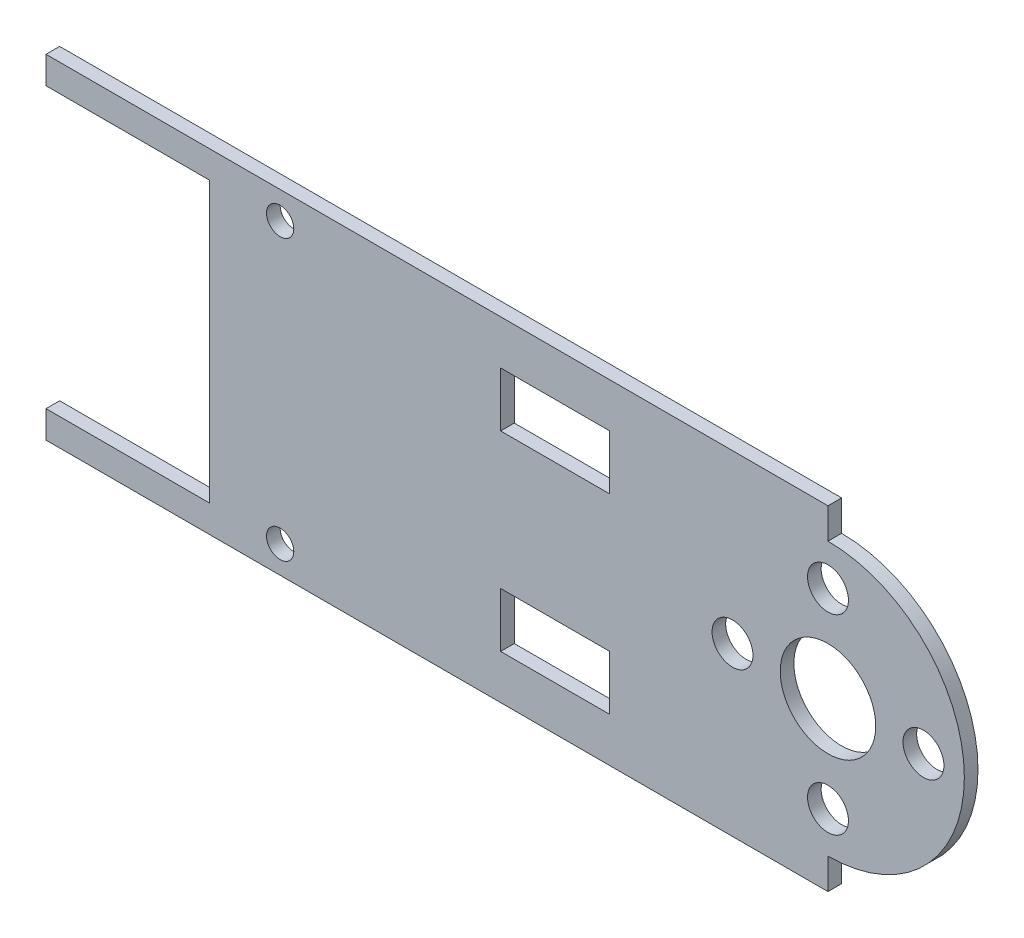
SolidWorks part; units mm, degrees
ref_plane "Front Plane" through (0, 0, 0) normal (0, 0, 1) x (1, 0, 0)
ref_plane "Top Plane" through (0, 0, 0) normal (0, 1, 0) x (1, 0, 0)
ref_plane "Right Plane" through (0, 0, 0) normal (1, 0, 0) x (0, 0, -1)
sketch "Sketch1" plane through (0, 0, 0) normal (0, 0, 1) x (1, 0, 0)
  line L0 (-5.1665, 12.25) -> (-17.1665, 12.25)
  line L1 (-5.1665, 12.25) -> (5.1665, 12.25)
  line L2 (-5.1665, 10.25) -> (-5.1665, -10.25)
  line L3 (-5.1665, -12.25) -> (5.1665, -12.25)
  line L5 (-5.1665, 12.25) -> (5.1665, -12.25) construction
  line L6 (-5.1665, -12.25) -> (5.1665, 12.25) construction
  line L7 (-17.1665, 12.25) -> (-17.1665, 10.25)
  line L8 (-17.1665, 10.25) -> (-5.1665, 10.25)
  line L9 (-5.1665, -12.25) -> (-17.1665, -12.25)
  line L10 (-17.1665, -12.25) -> (-17.1665, -10.25)
  line L11 (-17.1665, -10.25) -> (-5.1665, -10.25)
  line L12 (5.1665, 12.25) -> (40.1665, 12.25)
  line L13 (40.1665, 12.25) -> (40.1665, 10)
  line L14 (40.1665, -12.25) -> (5.1665, -12.25)
  line L16 (40.1665, -10) -> (40.1665, -12.25)
  line L17 (16.1665, 9) -> (24.1665, 9)
  line L18 (16.1665, 9) -> (16.1665, 5)
  line L19 (16.1665, 5) -> (24.1665, 5)
  line L20 (24.1665, 9) -> (24.1665, 5)
  line L21 (16.1665, 9) -> (24.1665, 5) construction
  line L22 (16.1665, 5) -> (24.1665, 9) construction
  line L23 (16.1665, -5) -> (24.1665, -5)
  line L24 (16.1665, -5) -> (16.1665, -9)
  line L25 (16.1665, -9) -> (24.1665, -9)
  line L26 (24.1665, -5) -> (24.1665, -9)
  line L27 (16.1665, -5) -> (24.1665, -9) construction
  line L28 (16.1665, -9) -> (24.1665, -5) construction
  circle A0 centre (0, 10.25) radius 1
  circle A1 centre (0, -10.25) radius 1
  arc A2 (40.1665, -10) -> (40.1665, 10) centre (40.1665, 0) ccw
  circle A3 centre (40.1665, 7) radius 1.5
  circle A4 centre (47.1665, 0) radius 1.5
  circle A5 centre (40.1665, -7) radius 1.5
  circle A6 centre (33.1665, 0) radius 1.5
  circle A7 centre (40.1665, 0) radius 3.5
  point P4 (0, 0)
  point P22 (20.1665, 7)
  point P35 (20.1665, -7)
  point P40 (0, 0)
  point P41 (0, 0)
  point P42 (0, 0)
  dimension "D3" = 2
  dimension "D4" = 2
  dimension "D11" = 20
  dimension "D12" = 3
  dimension "D15" = 7
  dimension "D1" = 20.5
  dimension "D2" = 10.25
  dimension "D5" = 2
  dimension "D6" = 2
  dimension "D7" = 2
  dimension "D8" = 12
  dimension "D9" = 12
  dimension "D10" = 35
  dimension "D13" = 7
  dimension "D16" = 0
  dimension "D17" = 3.25
  dimension "D18" = 3.25
  dimension "D19" = 20
  dimension "D20" = 4
  dimension "D21" = 4
  dimension "D22" = 8
  dimension "D23" = 8
  dimension "D14" = 4
extrude "Boss-Extrude1" add sketch "Sketch1" along normal blind 1
